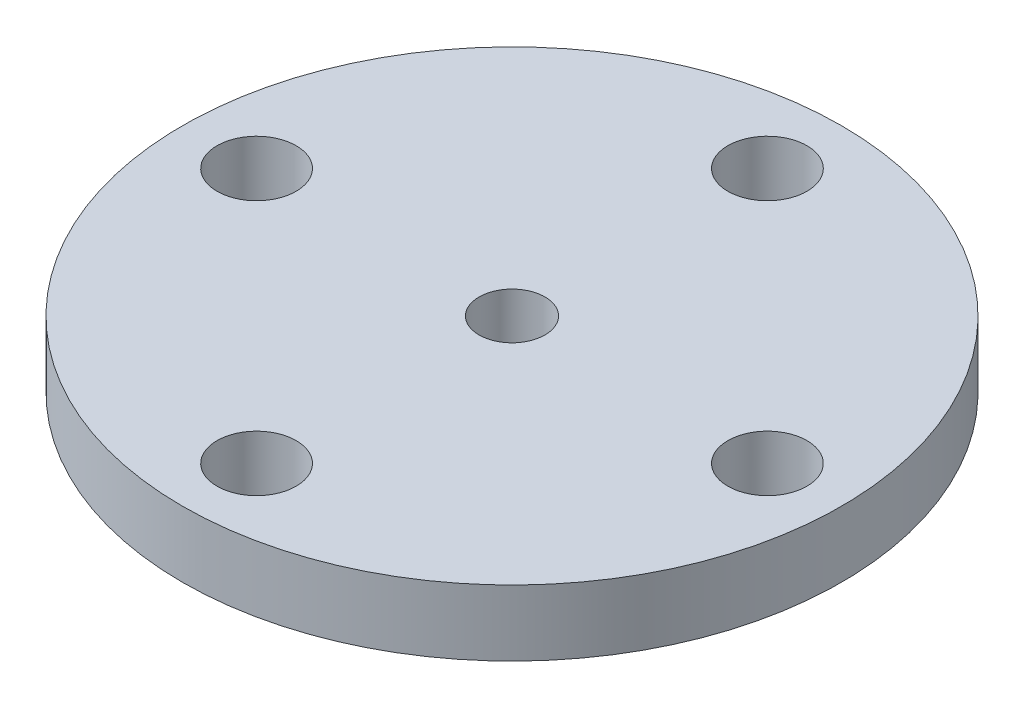
SolidWorks part; units mm, degrees
ref_plane "前视基准面" through (0, 0, 0) normal (0, 0, 1) x (1, 0, 0)
ref_plane "上视基准面" through (0, 0, 0) normal (0, 1, 0) x (1, 0, 0)
ref_plane "右视基准面" through (0, 0, 0) normal (1, 0, 0) x (0, 0, -1)
other "Configuration Table"
sketch "草图1" plane through (0, 0, 0) normal (0, 1, 0) x (1, 0, 0)
  line L0 (-5, 0) -> (-2.75, 0)
  circle A0 centre (0, 0) radius 2.75
  circle A1 centre (0, 0) radius 5
  circle A2 centre (0, 0) radius 0.5
  circle A3 centre (-3.875, 0) radius 0.35
  circle A4 centre (-3.875, 0) radius 0.6
  dimension "D1" = 10
  dimension "D2" = 5.5
  dimension "D3" = 1
  dimension "D4" = 0.7
  dimension "D5" = 1.2
extrude "凸台-拉伸1" add sketch "草图1" along normal blind 1 contours A1
extrude "切除-拉伸2" cut sketch "草图1<6>" along normal through all contours A2
sketch "草图1<6>" plane through (0, 0, 0) normal (0, 1, 0) x (1, 0, 0) same geometry as "草图1"
extrude "切除-拉伸3" cut sketch "草图1<7>" along normal blind 2 contours A4
sketch "草图1<7>" plane through (0, 0, 0) normal (0, 1, 0) x (1, 0, 0) same geometry as "草图1"
pattern_circular "阵列(圆周)1" count 4 over 360 about axis through (0, 1, 0) along (0, -1, 0) of "切除-拉伸3" reverse direction yes
